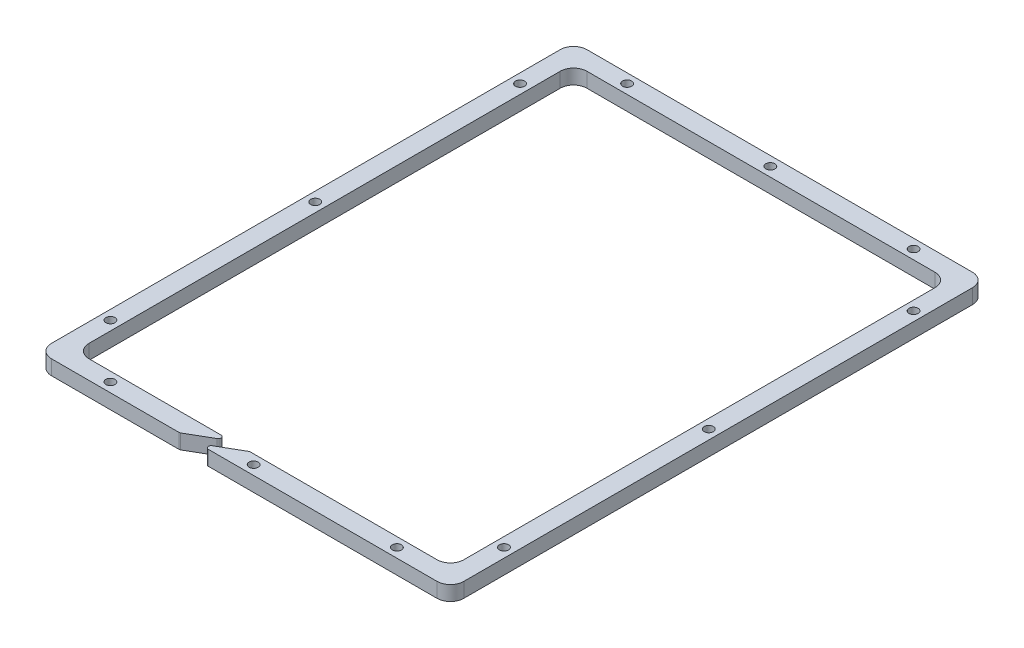
SolidWorks part; units mm, degrees
ref_plane "Front Plane" through (0, 0, 0) normal (0, 0, 1) x (1, 0, 0)
ref_plane "Top Plane" through (0, 0, 0) normal (0, 1, 0) x (1, 0, 0)
ref_plane "Right Plane" through (0, 0, 0) normal (1, 0, 0) x (0, 0, -1)
sketch "Sketch1" plane through (0, 0, 0) normal (0, 1, 0) x (1, 0, 0)
  line L0 (-80, 101) -> (-80, -101) construction
  line L1 (-70, -93) -> (70, -93)
  line L2 (-70, -93) -> (-70, 93)
  line L3 (-70, 93) -> (70, 93)
  line L4 (70, -93) -> (70, 93)
  line L5 (-70, -93) -> (70, 93) construction
  line L6 (-70, 93) -> (70, -93) construction
  line L7 (77, -100) -> (-77, -100)
  line L8 (77, -100) -> (77, 100)
  line L9 (77, 100) -> (-77, 100)
  line L10 (-77, -100) -> (-77, 100)
  line L11 (77, -100) -> (-77, 100) construction
  line L12 (77, 100) -> (-77, -100) construction
  line L13 (-78, -103) -> (78, -103) construction
  line L14 (68, 93) -> (-68, 93) construction
  line L15 (-70, 91) -> (-70, -91) construction
  point P0 (0, 0)
  point P5 (0, 0)
  dimension "D3" = 3
  dimension "D4" = 3
extrude "Boss-Extrude1" add sketch "Sketch1" along normal blind 5.5
ref_axis "Axis2" through (0, -0.275, 0) along (0, 1, 0)
fillet "Fillet1" radius 5 8 edges at (77, 2.75, -100) (77, 2.75, 100) (-77, 2.75, -100) (-77, 2.75, 100) (70, 2.75, -93) (70, 2.75, 93) (-70, 2.75, 93) (-70, 2.75, -93)
ref_plane "Plane1" through (0, 2.75, 0) normal (0, 1, 0) x (1, 0, 0)
sketch "Sketch3" plane through (0, 0, 0) normal (0, -1, 0) x (1, 0, 0)
  line L0 (0, 100) -> (0, 96.5) construction
  line L1 (73.5, 96.5) -> (-73.5, 96.5) construction
  line L2 (73.5, 96.5) -> (73.5, -96.5) construction
  line L3 (73.5, -96.5) -> (-73.5, -96.5) construction
  line L4 (-73.5, 96.5) -> (-73.5, -96.5) construction
  line L5 (-72, 100) -> (72, 100) construction
  line L6 (0, 96.5) -> (0, 93) construction
  line L7 (-65, 93) -> (65, 93) construction
  line L8 (77, 0) -> (73.5, 0) construction
  line L9 (77, 95) -> (77, -95) construction
  line L10 (73.5, 0) -> (70, 0) construction
  line L11 (70, 88) -> (70, -88) construction
  line L12 (-70, 0) -> (-73.5, 0) construction
  line L13 (-70, -88) -> (-70, 88) construction
  line L14 (0, -96.5) -> (0, -93) construction
  line L15 (65, -93) -> (-65, -93) construction
  circle A0 centre (73.5, -76.5) radius 1.7
  circle A1 centre (53.5, -96.5) radius 1.7
  circle A2 centre (-53.5, -96.5) radius 1.7
  circle A3 centre (-73.5, -76.5) radius 1.7
  circle A4 centre (-73.5, 0) radius 1.7
  circle A5 centre (-73.5, 76.5) radius 1.7
  circle A6 centre (-53.5, 96.5) radius 1.7
  circle A7 centre (53.5, 96.5) radius 1.7
  circle A8 centre (73.5, 76.5) radius 1.7
  circle A9 centre (73.5, 0) radius 1.7
  circle A10 centre (0, -96.5) radius 1.7
  circle A11 centre (0, 96.5) radius 1.7
  dimension "D1" = 3.4
  dimension "D5" = 73.5
  dimension "D2" = 96.5
  dimension "D3" = 20
  dimension "D4" = 20
  dimension "D6" = 20
  dimension "D7" = 20
extrude "Cut-Extrude1" cut sketch "Sketch3" against normal through all
sketch "Sketch4" plane through (0, 5.5, 0) normal (0, 1, 0) x (1, 0, 0)
  line L0 (-17.1244, -100) -> (-5, -93)
  line L1 (-72, -100) -> (72, -100) construction
  line L2 (-65, -93) -> (65, -93) construction
  line L3 (-12, -93) -> (-5, -93)
  line L4 (-24.1244, -100) -> (-12, -93)
  line L5 (-24.1244, -100) -> (-17.1244, -100)
  circle A0 centre (0, -96.5) radius 1.7 construction
  dimension "D1" = 3.5
  dimension "D2" = 30
  dimension "D3" = 5
extrude "Cut-Extrude2" cut sketch "Sketch4" against normal through all
fillet "Fillet2" radius 1 4 edges at (-24.1244, 2.75, 100) (-12, 2.75, 93) (-5, 2.75, 93) (-17.1244, 2.75, 100)
